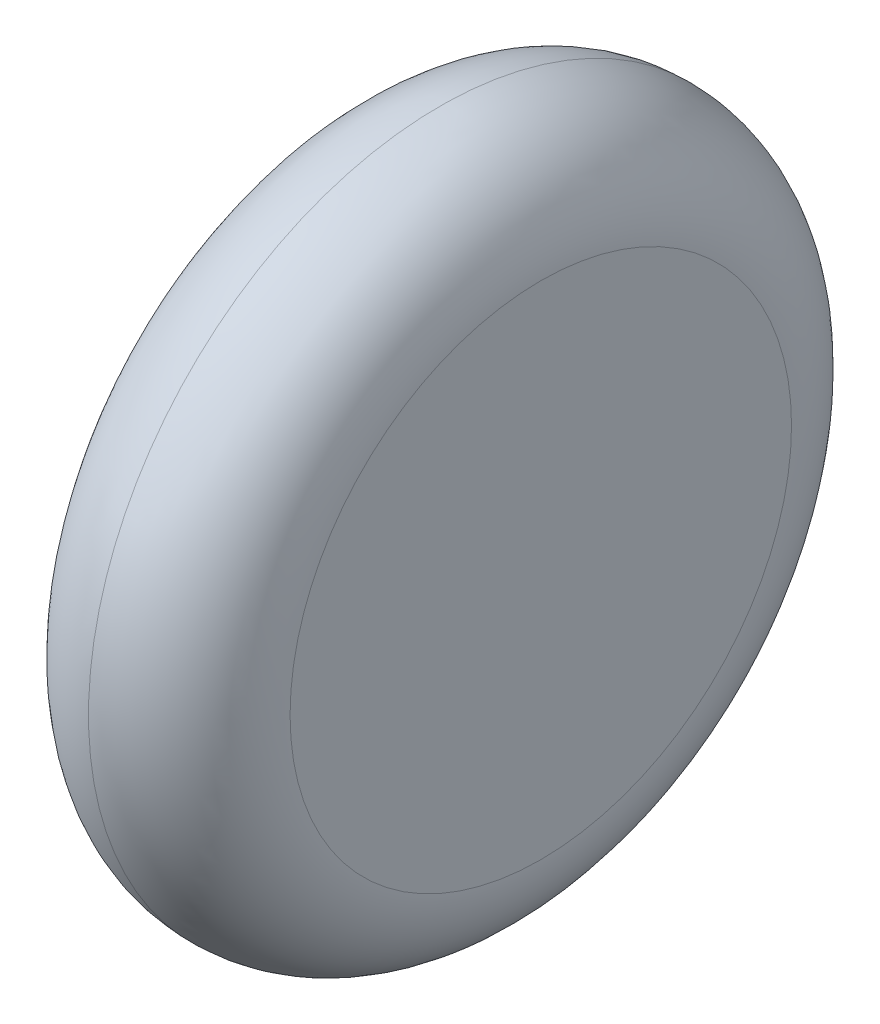
SolidWorks part; units mm, degrees
ref_plane "Front Plane" through (0, 0, 0) normal (0, 0, 1) x (1, 0, 0)
ref_plane "Top Plane" through (0, 0, 0) normal (0, 1, 0) x (1, 0, 0)
ref_plane "Right Plane" through (0, 0, 0) normal (1, 0, 0) x (0, 0, -1)
sketch "Sketch2" plane through (0, 0, 0) normal (1, 0, 0) x (0, 0, -1)
  circle A0 centre (0, 0) radius 708.66
  dimension "D1" = 1417.32
extrude "Boss-Extrude1" add sketch "Sketch2" along normal mid plane 406.4
fillet "Fillet1" radius 203.2 2 edges at (-203.2, 0, -708.66) (203.2, 0, -708.66)
